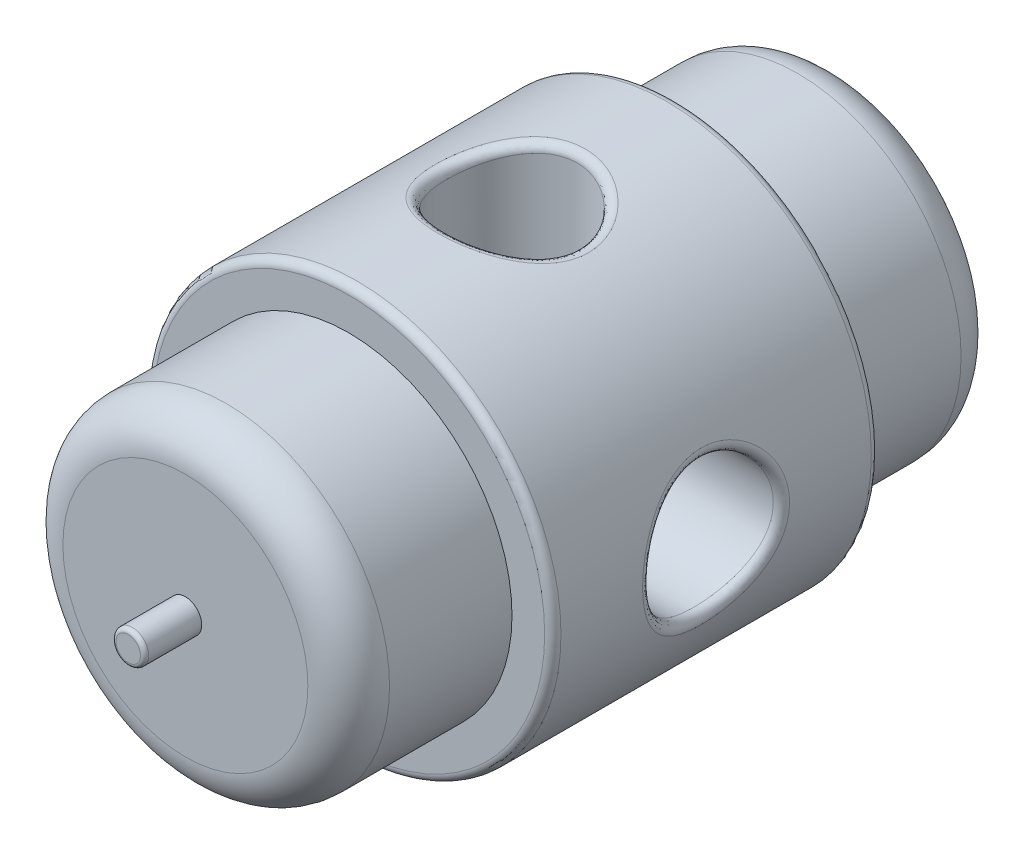
SolidWorks part; units mm, degrees
material "ABS PC"
ref_plane "Front Plane" through (0, 0, 0) normal (0, 0, 1) x (1, 0, 0)
ref_plane "Top Plane" through (0, 0, 0) normal (0, 1, 0) x (1, 0, 0)
ref_plane "Right Plane" through (0, 0, 0) normal (1, 0, 0) x (0, 0, -1)
ref_plane "Plane1" through (0, 0, 150) normal (0, 0, 1) x (1, 0, 0)
sketch "Sketch2" plane through (0, 0, 150) normal (0, 0, 1) x (1, 0, 0)
  line L0 (-75, 200) -> (-75, 100)
  line L1 (-200, 200) -> (200, 200) construction
  line L2 (-200, 200) -> (-200, -200) construction
  line L3 (-200, -200) -> (200, -200) construction
  line L4 (200, 200) -> (200, -200) construction
  line L5 (-200, 200) -> (200, -200) construction
  line L6 (-200, -200) -> (200, 200) construction
  line L7 (35, 200) -> (47.5, 200)
  line L8 (47.5, 200) -> (47.5, 150)
  line L9 (-35, 200) -> (-35, 150)
  line L10 (-35, 150) -> (35, 150)
  line L11 (35, 150) -> (35, 200)
  line L12 (47.5, 150) -> (62.5, 150)
  line L13 (-75, 200) -> (-62.5, 200)
  line L14 (-62.5, 200) -> (-62.5, 150)
  line L15 (-62.5, 150) -> (-47.5, 150)
  line L16 (-47.5, 150) -> (-47.5, 200)
  line L17 (-47.5, 200) -> (-35, 200)
  line L18 (62.5, 150) -> (62.5, 200)
  line L19 (62.5, 200) -> (75, 200)
  line L20 (75, 200) -> (75, 100)
  line L21 (100, 75) -> (200, 75)
  line L22 (200, 75) -> (200, 62.5)
  line L23 (200, 62.5) -> (150, 62.5)
  line L24 (150, 62.5) -> (150, 47.5)
  line L25 (150, 47.5) -> (200, 47.5)
  line L26 (200, 47.5) -> (200, 35)
  line L27 (200, 35) -> (150, 35)
  line L28 (150, 35) -> (150, -35)
  line L29 (150, -35) -> (200, -35)
  line L30 (200, -35) -> (200, -47.5)
  line L31 (200, -47.5) -> (150, -47.5)
  line L32 (150, -47.5) -> (150, -62.5)
  line L33 (150, -62.5) -> (200, -62.5)
  line L34 (200, -62.5) -> (200, -75)
  line L35 (200, -75) -> (100, -75)
  line L36 (100, -75) -> (75, -100)
  line L37 (75, -100) -> (75, -200)
  line L38 (75, -200) -> (62.5, -200)
  line L39 (62.5, -200) -> (62.5, -150)
  line L40 (62.5, -150) -> (47.5, -150)
  line L41 (47.5, -150) -> (47.5, -200)
  line L42 (47.5, -200) -> (35, -200)
  line L43 (35, -200) -> (35, -150)
  line L44 (35, -150) -> (-35, -150)
  line L45 (-35, -150) -> (-35, -200)
  line L46 (-35, -200) -> (-47.5, -200)
  line L47 (-47.5, -200) -> (-47.5, -150)
  line L48 (-47.5, -150) -> (-62.5, -150)
  line L49 (-62.5, -150) -> (-62.5, -200)
  line L50 (-62.5, -200) -> (-75, -200)
  line L51 (-75, -200) -> (-75, -100)
  line L52 (-75, -100) -> (-100, -75)
  line L53 (-100, -75) -> (-200, -75)
  line L54 (-200, -75) -> (-200, -62.5)
  line L55 (-200, -62.5) -> (-150, -62.5)
  line L56 (-150, -62.5) -> (-150, -47.5)
  line L57 (-150, -47.5) -> (-200, -47.5)
  line L58 (-200, -47.5) -> (-200, -35)
  line L59 (-200, -35) -> (-150, -35)
  line L60 (-150, -35) -> (-150, 35)
  line L61 (-150, 35) -> (-200, 35)
  line L62 (-200, 35) -> (-200, 47.5)
  line L63 (-200, 47.5) -> (-150, 47.5)
  line L64 (-150, 47.5) -> (-150, 62.5)
  line L65 (-150, 62.5) -> (-200, 62.5)
  line L66 (-200, 62.5) -> (-200, 75)
  line L67 (-200, 75) -> (-100, 75)
  line L68 (-100, 75) -> (-75, 100)
  line L69 (75, 100) -> (100, 75)
  point P0 (0, 0)
  point P8 (0, 150)
  point P72 (150, 0)
  point P74 (0, -150)
  point P75 (-150, 0)
  dimension "D1" = 400
  dimension "D2" = 400
  dimension "D3" = 12.5
  dimension "D4" = 40
  dimension "D5" = 12.5
  dimension "D6" = 70
  dimension "D7" = 50
  dimension "D8" = 50
  dimension "D9" = 100
  dimension "D10" = 50
  dimension "D11" = 12.5
  dimension "D12" = 12.5
  dimension "D13" = 15
  dimension "D14" = 100
  dimension "D15" = 70
  dimension "D16" = 12.5
  dimension "D17" = 12.5
  dimension "D18" = 15
  dimension "D19" = 12.5
  dimension "D20" = 12.5
  dimension "D21" = 15
  dimension "D22" = 50
  dimension "D23" = 50
  dimension "D24" = 50
  dimension "D25" = 100
  dimension "D26" = 12.5
  dimension "D27" = 12.5
  dimension "D28" = 15
  dimension "D29" = 12.5
  dimension "D30" = 12.5
  dimension "D31" = 15
  dimension "D32" = 70
  dimension "D33" = 100
  dimension "D34" = 100
  dimension "D35" = 12.5
  dimension "D36" = 12.5
  dimension "D37" = 12.5
  dimension "D38" = 12.5
  dimension "D39" = 15
  dimension "D40" = 15
  dimension "D41" = 70
  dimension "D42" = 100
  dimension "D43" = 100
  dimension "D44" = 100
  dimension "D45" = 50
  dimension "D46" = 50
  dimension "D47" = 50
  dimension "D48" = 50
  dimension "D49" = 50
  dimension "D50" = 50
sketch "Sketch20" plane through (0, 0, 150) normal (0, 0, 1) x (1, 0, 0)
  circle A0 centre (200, 200) radius 25
extrude "Boss-Extrude6" add sketch "Sketch20" against normal blind 40 separate body
ref_plane "Plane2" through (0, 210, 0) normal (0, 1, 0) x (1, 0, 0)
sketch "Sketch21" plane through (0, 210, 0) normal (0, 1, 0) x (1, 0, 0)
  line L0 (225, -110) -> (175, -110) construction
  line L1 (225, -150) -> (225, -110) construction
  circle A0 centre (200, -130) radius 8
  dimension "D1" = 20
  dimension "D2" = 25
extrude "Cut-Extrude2" cut sketch "Sketch21" along normal blind 26
ref_axis "Axis1" through (200, 200, 110) along (0, 0, 1)
pattern_circular "CirPattern1" count 2 every 90 about axis through (200, 200, 110) along (0, 0, 1) of "Cut-Extrude2" reverse direction yes
sketch "Sketch24" plane through (0, 0, 150) normal (0, 0, 1) x (1, 0, 0)
  circle A0 centre (200, 200) radius 20
extrude "Boss-Extrude7" add sketch "Sketch24" along normal blind 20 separate body contours A0
fillet "Fillet3" radius 5 1 edges at (220, 200, 170)
sketch "Sketch25" plane through (0, 0, 170) normal (0, 0, 1) x (1, 0, 0)
  circle A0 centre (200, 200) radius 2
extrude "Boss-Extrude8" add sketch "Sketch25" along normal blind 7
fillet "Fillet4" radius 0.5 1 edges at (202, 200, 177)
fillet "Fillet5" radius 1 4 edges at (224.961, 201.3957, 137.8773) (198.6043, 224.961, 137.8773) (225, 200, 110) (225, 200, 150)
sketch "Sketch26" plane through (0, 0, 110) normal (0, 0, -1) x (-1, 0, 0)
  circle A0 centre (-200, 200) radius 20
extrude "Boss-Extrude9" add sketch "Sketch26" along normal blind 20 separate body
sketch "Sketch27" plane through (0, 0, 90) normal (0, 0, -1) x (1, 0, 0)
  circle A0 centre (200, -200) radius 2
extrude "Boss-Extrude10" add sketch "Sketch27" along normal blind 7
fillet "Fillet6" radius 0.5 1 edges at (198, 200, 83)
fillet "Fillet7" radius 5 1 edges at (180, 200, 90)
